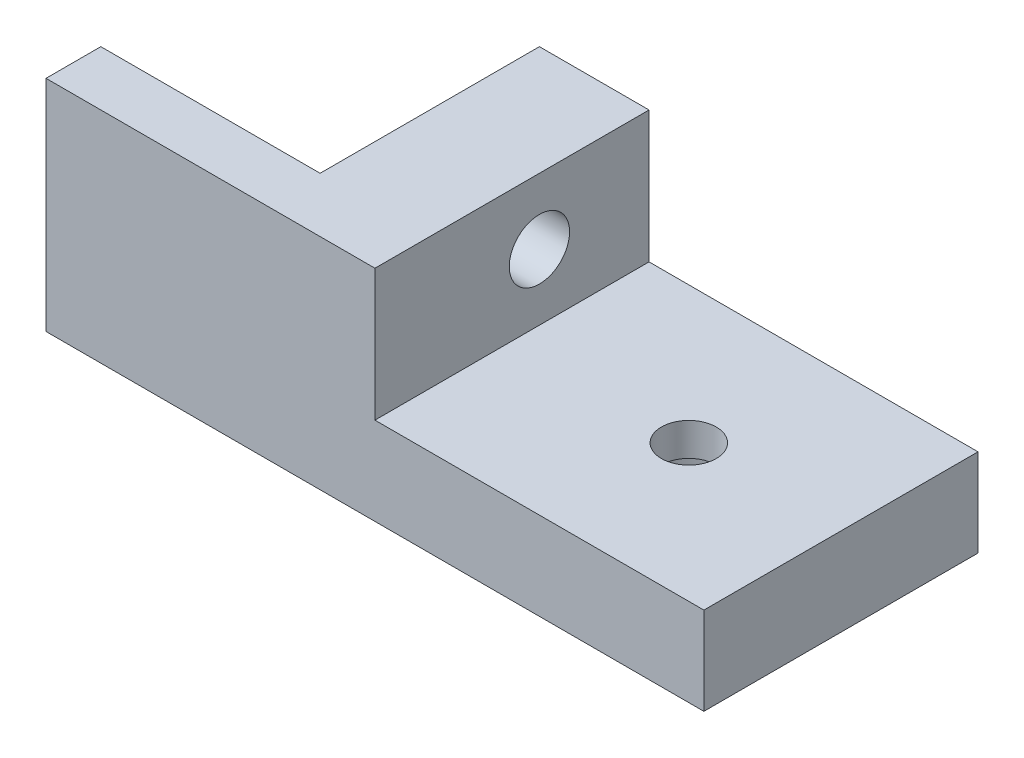
SolidWorks part; units mm, degrees
ref_plane "Front Plane" through (0, 0, 0) normal (0, 0, 1) x (1, 0, 0)
ref_plane "Top Plane" through (0, 0, 0) normal (0, 1, 0) x (1, 0, 0)
ref_plane "Right Plane" through (0, 0, 0) normal (1, 0, 0) x (0, 0, -1)
sketch "Sketch1" plane through (0, 0, 0) normal (0, 1, 0) x (1, 0, 0)
  line L1 (0, 0) -> (60, 0)
  line L2 (0, 0) -> (0, 5)
  line L3 (20, 25) -> (60, 25)
  line L4 (60, 0) -> (60, 25)
  line L7 (0, 5) -> (20, 5)
  line L8 (20, 25) -> (20, 5)
  dimension "D2" = 60
extrude "Boss-Extrude1" add sketch "Sketch1" along normal blind 20
sketch "Sketch2" plane through (0, 20, 0) normal (0, 1, 0) x (1, 0, 0)
  line L0 (20, 25) -> (20, 5) construction
  line L1 (60, 25) -> (30, 25)
  line L2 (60, 25) -> (60, 0)
  line L3 (60, 0) -> (30, 0)
  line L4 (30, 25) -> (30, 0)
  dimension "D1" = 25
  dimension "D2" = 10
extrude "Cut-Extrude1" cut sketch "Sketch2" against normal blind 12
sketch "Sketch3" plane through (0, 8, 0) normal (0, 1, 0) x (1, 0, 0)
  line L0 (30, 25) -> (30, 0) construction
  circle A0 centre (46.1, 12.5258) radius 11.1
  dimension "D1" = 22.2
  dimension "D2" = 5
sketch "Sketch5" plane through (30, 0, 0) normal (1, 0, 0) x (0, 0, -1)
  line L0 (25, 20) -> (0, 20) construction
  line L2 (5, 20) -> (5, 0) construction
  circle A0 centre (15, 14) radius 2.75
  point P4 (12.5, 20)
  point P5 (0, 0)
  dimension "D1" = 5.5
  dimension "D2" = 6
  dimension "D3" = 10
extrude "Cut-Extrude4" cut sketch "Sketch5" against normal through all
sketch "Sketch6" plane through (0, 0, 0) normal (0, -1, 0) x (1, 0, 0)
  circle A0 centre (46.1, -12.5258) radius 6.7
  dimension "D1" = 13.4
extrude "Cut-Extrude5" cut sketch "Sketch6" against normal blind 5
sketch "Sketch7" plane through (0, 5, 0) normal (0, -1, 0) x (1, 0, 0)
  circle A0 centre (46.1, -12.5258) radius 2.5
  dimension "D1" = 5
extrude "Cut-Extrude6" cut sketch "Sketch7" against normal through all
